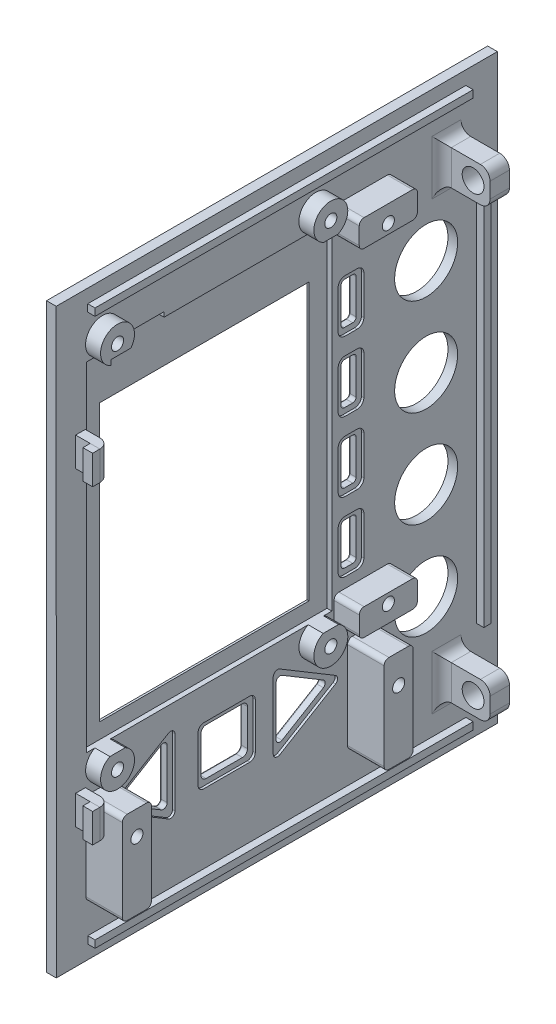
SolidWorks part; units mm, degrees
ref_plane "Front Plane" through (0, 0, 0) normal (0, 0, 1) x (1, 0, 0)
ref_plane "Top Plane" through (0, 0, 0) normal (0, 1, 0) x (1, 0, 0)
ref_plane "Right Plane" through (0, 0, 0) normal (1, 0, 0) x (0, 0, -1)
ref_plane "Plane2" through (-1175.548, -0.0877, 0) normal (-1, -0.0001, 0) x (0, 0, 1)
sketch "Sketch2" plane through (-1175.548, -0.0877, 0) normal (-1, -0.0001, 0) x (0, 0, 1)
  line L0 (-1289.195, -889.282) -> (-1289.195, -789.282) construction
  line L1 (-1204.195, -779.282) -> (-1295.195, -779.282)
  line L2 (-1204.195, -779.282) -> (-1204.195, -899.282)
  line L3 (-1204.195, -899.282) -> (-1295.195, -899.282)
  line L4 (-1295.195, -779.282) -> (-1295.195, -899.282)
  line L5 (-1289.195, -889.282) -> (-1287.685, -889.282) construction
  line L6 (-1289.195, -789.282) -> (-1287.685, -789.282) construction
  circle A0 centre (-1280.5, -869.282) radius 6.5
  circle A1 centre (-1280.5, -849.282) radius 6.5
  circle A2 centre (-1280.5, -829.282) radius 6.5
  circle A3 centre (-1280.5, -809.282) radius 6.5
  ellipse E0 centre (-1280.5, -869.282) end of major axis (-1281.15, -869.2796) minor radius 0.65 construction
  ellipse E1 centre (-1280.5, -849.282) end of major axis (-1281.15, -849.2796) minor radius 0.65 construction
  ellipse E2 centre (-1280.5, -829.282) end of major axis (-1281.15, -829.2796) minor radius 0.65 construction
  ellipse E3 centre (-1280.5, -809.282) end of major axis (-1281.15, -809.2796) minor radius 0.65 construction
  ellipse E4 centre (-1280.5, -869.282) end of major axis (-1281.15, -869.2796) minor radius 0.65
  ellipse E5 centre (-1280.5, -849.282) end of major axis (-1281.15, -849.2796) minor radius 0.65 construction
  ellipse E6 centre (-1280.5, -829.282) end of major axis (-1281.15, -829.2796) minor radius 0.65
  ellipse E7 centre (-1280.5, -809.282) end of major axis (-1281.15, -809.2796) minor radius 0.65
  dimension "D5" = 13
  dimension "D6" = 13
  dimension "D7" = 13
  dimension "D8" = 13
  dimension "D1" = 6
  dimension "D2" = 10
  dimension "D3" = 10
  dimension "D4" = 91
extrude "Boss-Extrude2" add sketch "Sketch2" along normal blind 2 contours L1 L4 L3 L2 A3 A2 A1 A0 region at (-1175.4854, -839.3697, -1248.1207)
sketch "Sketch3" plane through (-1177.548, -0.0879, 0) normal (-1, -0.0001, 0) x (0, 0, 1)
  line L12 (-1214.15, -858.982) -> (-1257.35, -858.982) construction
  line L13 (-1257.35, -858.982) -> (-1257.35, -802.002) construction
  line L14 (-1214.15, -802.002) -> (-1214.15, -858.982) construction
  line L15 (-1257.35, -802.002) -> (-1214.15, -802.002) construction
  line L16 (-1214.15, -858.982) -> (-1257.35, -858.982)
  line L17 (-1257.35, -858.982) -> (-1257.35, -802.002)
  line L18 (-1214.15, -802.002) -> (-1214.15, -858.982)
  line L19 (-1257.35, -802.002) -> (-1214.15, -802.002)
extrude "tft_cutout" cut sketch "Sketch3" against normal through all
sketch "tft_inset_cutout" plane through (-1175.548, -0.0877, 0) normal (1, 0.0001, 0) x (0, 0, -1)
  line L4 (1210.95, -792.861) -> (1210.95, -861.661) construction
  line L5 (1260.55, -792.861) -> (1210.95, -792.861) construction
  line L12 (1260.55, -861.661) -> (1260.55, -792.861) construction
  line L17 (1210.95, -861.661) -> (1260.55, -861.661) construction
  line L18 (1260.55, -861.661) -> (1260.55, -792.861) construction
  line L19 (1210.95, -861.661) -> (1260.55, -861.661) construction
  line L20 (1210.95, -792.861) -> (1210.95, -861.661) construction
  line L21 (1260.55, -792.861) -> (1210.95, -792.861) construction
  line L22 (1261.05, -792.361) -> (1210.45, -792.361)
  line L26 (1212.45, -792.861) -> (1226.45, -792.861)
  line L27 (1212.45, -792.861) -> (1212.45, -791.361)
  line L28 (1212.45, -791.361) -> (1226.45, -791.361)
  line L29 (1226.45, -792.861) -> (1226.45, -791.361)
  line L30 (1210.45, -792.361) -> (1210.45, -862.161)
  line L31 (1210.45, -862.161) -> (1261.05, -862.161)
  line L32 (1261.05, -862.161) -> (1261.05, -792.361)
  line M40 (1257.35, -858.982) -> (1214.15, -858.982)
  line M41 (1214.15, -858.982) -> (1214.15, -802.002)
  line M42 (1214.15, -802.002) -> (1257.35, -802.002)
  line M43 (1257.35, -802.002) -> (1257.35, -858.982)
  dimension "D3" = 1.5
  dimension "D4" = 0.5
  dimension "D1" = 14
  dimension "D2" = 1.5
extrude "Cut-Extrude2" cut sketch "tft_inset_cutout" against normal up to surface (1 mm away) contours L18 | L31 L32 L22 L29 L26 L27 L30 M43 M40 M41 M42 | L26 L29 L22 L27 | L22 L29 L28 L27 region at (-1175.4863, -827.3487, -1260.1879) region at (-1175.4889, -792.6987, -1219.45) region at (-1175.4889, -791.9487, -1219.45)
chamfer "Chamfer2" distance 1 angle 30 4 edges at (-1177.486, -830.5799, -1257.35) (-1177.4839, -859.0699, -1235.75) (-1177.486, -830.5799, -1214.15) (-1177.4882, -802.0899, -1235.75) first distance on face at (-1177.486, -830.5799, -1235.75)
sketch "Sketch6" plane through (-1175.548, -0.0877, 0) normal (1, 0.0001, 0) x (0, 0, -1)
  line L5 (1261.5, -864.9905) -> (1273.5, -864.9905)
  line L6 (1261.5, -864.9905) -> (1261.5, -859.4905)
  line L7 (1261.5, -859.4905) -> (1273.5, -859.4905)
  line L8 (1261.5, -864.9905) -> (1273.5, -864.9905)
  line L9 (1273.5, -864.9905) -> (1273.5, -789.9905)
  line L10 (1273.5, -789.9905) -> (1261.5, -789.9905)
  line L11 (1261.5, -789.9905) -> (1261.5, -864.9905)
  line L12 (1261.5, -864.9905) -> (1273.5, -864.9905) construction
  line L13 (1273.5, -864.9905) -> (1273.5, -789.9905) construction
  line L14 (1273.5, -789.9905) -> (1261.5, -789.9905) construction
  line L15 (1261.5, -789.9905) -> (1261.5, -864.9905) construction
  line L16 (1273.5, -864.9905) -> (1273.5, -859.4905)
  line L17 (1261.5, -789.9905) -> (1273.5, -789.9905)
  line L18 (1261.5, -789.9905) -> (1261.5, -795.4905)
  line L19 (1261.5, -795.4905) -> (1273.5, -795.4905)
  line L20 (1273.5, -789.9905) -> (1273.5, -795.4905)
  circle A0 centre (1267.5, -861.4905) radius 1.25 construction
  circle A1 centre (1267.5, -861.4905) radius 1.25 construction
  circle A2 centre (1267.5, -861.4905) radius 1.25
  circle A3 centre (1267.5, -793.4905) radius 1.25 construction
  circle A4 centre (1267.5, -793.4905) radius 1.25 construction
  circle A5 centre (1267.5, -793.4905) radius 1.25
  dimension "D2" = 2.5
  dimension "D4" = 2.5
  dimension "D3" = 2
  dimension "D5" = 2
extrude "menu_standoffs" add sketch "Sketch6" along normal up to surface (5.203 mm away)
fillet "Fillet1" radius 1 8 edges at (-1172.8871, -795.5781, -1261.5) (-1172.8871, -795.5781, -1273.5) (-1172.8875, -790.0781, -1273.5) (-1172.8875, -790.0781, -1261.5) (-1172.8824, -859.5781, -1273.5) (-1172.8824, -859.5781, -1261.5) (-1172.882, -865.0781, -1261.5) (-1172.882, -865.0781, -1273.5)
sketch "Sketch7" plane through (-1170.345, -0.0874, 0) normal (1, 0.0001, 0) x (0, 0, -1)
  circle A0 centre (1267.5, -861.4905) radius 1.25 construction
  circle A1 centre (1267.5, -793.4905) radius 1.25 construction
  circle A2 centre (1267.5, -861.4905) radius 1.25
  circle A3 centre (1267.5, -793.4905) radius 1.25
extrude "menu_standoff_holes" [suppressed] cut sketch "Sketch7" against normal blind 5 contours A2
sketch "Sketch8" plane through (-1175.548, -0.0877, 0) normal (1, 0.0001, 0) x (0, 0, -1)
  circle A0 centre (1213.75, -865.282) radius 1.55 construction
  circle A1 centre (1257.75, -865.282) radius 1.55 construction
  circle A2 centre (1257.75, -789.202) radius 1.55 construction
  circle A3 centre (1213.75, -789.2023) radius 1.55 construction
  circle A4 centre (1213.75, -865.282) radius 1.55 construction
  circle A5 centre (1257.75, -865.282) radius 1.55 construction
  circle A6 centre (1257.75, -789.202) radius 1.55 construction
  circle A7 centre (1213.75, -789.2023) radius 1.55 construction
  circle A8 centre (1213.75, -789.2023) radius 3.5
  circle A9 centre (1257.75, -789.202) radius 3.5
  circle A10 centre (1257.75, -865.282) radius 3.5
  circle A11 centre (1213.75, -865.282) radius 3.5
  circle A12 centre (1213.75, -789.2023) radius 1.25
  circle A13 centre (1213.75, -865.282) radius 1.25
  circle A14 centre (1257.75, -865.282) radius 1.25
  circle A15 centre (1257.75, -789.202) radius 1.25
  dimension "D2" = 2.5
  dimension "D1" = 7
extrude "TFT_standoffs" add sketch "Sketch8" along normal up to surface (3.09 mm away)
sketch "Sketch9" plane through (-1175.548, -0.0877, 0) normal (1, 0.0001, 0) x (0, 0, -1)
  circle A0 centre (1213.75, -789.2023) radius 1.25 construction
  circle A1 centre (1213.75, -865.282) radius 1.25 construction
  circle A2 centre (1257.75, -865.282) radius 1.25 construction
  circle A3 centre (1257.75, -789.202) radius 1.25 construction
  circle A4 centre (1213.75, -789.2023) radius 1.25
  circle A5 centre (1213.75, -865.282) radius 1.25
  circle A6 centre (1257.75, -865.282) radius 1.25
  circle A7 centre (1257.75, -789.202) radius 1.25
extrude "TFT_standoff_holes" cut sketch "Sketch9" against normal offset from surface (1 mm away) 1 up to face at (-1177.486, -830.5799, -1235.75)
extrude "Cut-Extrude5" cut sketch "Sketch5<3>" along normal through all contours L31 L32 L22 L29 L26 L27 L30 M43 M40 M41 M42 | L22 L29 L28 L27 | L26 L29 L22 L27 region at (-1175.4863, -827.3487, -1260.1879) region at (-1175.4889, -792.6987, -1219.45) region at (-1175.4889, -791.9487, -1219.45)
sketch "Sketch5<3>" plane through (-1175.548, -0.0877, 0) normal (1, 0.0001, 0) x (0, 0, -1) same geometry as "tft_inset_cutout"
sketch "Sketch10" plane through (-1175.548, -0.0877, 0) normal (1, 0.0001, 0) x (0, 0, -1)
  line L0 (1267.2535, -804.997) -> (1267.2535, -812.997) construction
  line L1 (1266.2535, -813.997) -> (1263.7535, -813.997) construction
  line L2 (1262.7535, -812.997) -> (1262.7535, -804.997) construction
  line L3 (1263.7535, -803.997) -> (1266.2535, -803.997) construction
  line L4 (1267.2535, -804.997) -> (1267.2535, -812.997) construction
  line L5 (1266.2535, -813.997) -> (1263.7535, -813.997) construction
  line L6 (1262.7535, -812.997) -> (1262.7535, -804.997) construction
  line L7 (1263.7535, -803.997) -> (1266.2535, -803.997) construction
  line L8 (1267.6535, -804.997) -> (1267.6535, -812.997)
  line L9 (1266.2535, -814.397) -> (1263.7535, -814.397)
  line L10 (1262.3535, -812.997) -> (1262.3535, -804.997)
  line L11 (1263.7535, -803.597) -> (1266.2535, -803.597)
  line L12 (1267.6535, -819.327) -> (1267.6535, -827.327)
  line L13 (1266.2535, -828.727) -> (1263.7535, -828.727)
  line L14 (1262.3535, -827.327) -> (1262.3535, -819.327)
  line L15 (1263.7535, -817.927) -> (1266.2535, -817.927)
  line L16 (1267.2535, -819.327) -> (1267.2535, -827.327) construction
  line L17 (1266.2535, -828.327) -> (1263.7535, -828.327) construction
  line L18 (1262.7535, -827.327) -> (1262.7535, -819.327) construction
  line L19 (1263.7535, -818.327) -> (1266.2535, -818.327) construction
  line L20 (1267.6535, -833.657) -> (1267.6535, -841.657)
  line L21 (1266.2535, -843.057) -> (1263.7535, -843.057)
  line L22 (1262.3535, -841.657) -> (1262.3535, -833.657)
  line L23 (1263.7535, -832.257) -> (1266.2535, -832.257)
  line L24 (1267.2535, -833.657) -> (1267.2535, -841.657) construction
  line L25 (1266.2535, -842.657) -> (1263.7535, -842.657) construction
  line L26 (1262.7535, -841.657) -> (1262.7535, -833.657) construction
  line L27 (1263.7535, -832.657) -> (1266.2535, -832.657) construction
  line L28 (1267.6535, -847.987) -> (1267.6535, -855.987)
  line L29 (1266.2535, -857.387) -> (1263.7535, -857.387)
  line L30 (1262.3535, -855.987) -> (1262.3535, -847.987)
  line L31 (1263.7535, -846.587) -> (1266.2535, -846.587)
  line L32 (1267.2535, -847.987) -> (1267.2535, -855.987) construction
  line L33 (1266.2535, -856.987) -> (1263.7535, -856.987) construction
  line L34 (1262.7535, -855.987) -> (1262.7535, -847.987) construction
  line L35 (1263.7535, -846.987) -> (1266.2535, -846.987) construction
  arc A0 (1267.2535, -804.997) -> (1266.2535, -803.997) centre (1266.2535, -804.997) ccw construction
  arc A1 (1266.2535, -813.997) -> (1267.2535, -812.997) centre (1266.2535, -812.997) ccw construction
  arc A2 (1262.7535, -812.997) -> (1263.7535, -813.997) centre (1263.7535, -812.997) ccw construction
  arc A3 (1263.7535, -803.997) -> (1262.7535, -804.997) centre (1263.7535, -804.997) ccw construction
  arc A4 (1267.2535, -804.997) -> (1266.2535, -803.997) centre (1266.2535, -804.997) ccw construction
  arc A5 (1266.2535, -813.997) -> (1267.2535, -812.997) centre (1266.2535, -812.997) ccw construction
  arc A6 (1262.7535, -812.997) -> (1263.7535, -813.997) centre (1263.7535, -812.997) ccw construction
  arc A7 (1263.7535, -803.997) -> (1262.7535, -804.997) centre (1263.7535, -804.997) ccw construction
  arc A8 (1266.2535, -814.397) -> (1267.6535, -812.997) centre (1266.2535, -812.997) ccw
  arc A9 (1262.3535, -812.997) -> (1263.7535, -814.397) centre (1263.7535, -812.997) ccw
  arc A10 (1263.7535, -803.597) -> (1262.3535, -804.997) centre (1263.7535, -804.997) ccw
  arc A11 (1267.6535, -804.997) -> (1266.2535, -803.597) centre (1266.2535, -804.997) ccw
  arc A12 (1266.2535, -828.727) -> (1267.6535, -827.327) centre (1266.2535, -827.327) ccw
  arc A13 (1262.3535, -827.327) -> (1263.7535, -828.727) centre (1263.7535, -827.327) ccw
  arc A14 (1263.7535, -817.927) -> (1262.3535, -819.327) centre (1263.7535, -819.327) ccw
  arc A15 (1267.6535, -819.327) -> (1266.2535, -817.927) centre (1266.2535, -819.327) ccw
  arc A16 (1267.2535, -819.327) -> (1266.2535, -818.327) centre (1266.2535, -819.327) ccw construction
  arc A17 (1266.2535, -828.327) -> (1267.2535, -827.327) centre (1266.2535, -827.327) ccw construction
  arc A18 (1262.7535, -827.327) -> (1263.7535, -828.327) centre (1263.7535, -827.327) ccw construction
  arc A19 (1263.7535, -818.327) -> (1262.7535, -819.327) centre (1263.7535, -819.327) ccw construction
  arc A20 (1266.2535, -843.057) -> (1267.6535, -841.657) centre (1266.2535, -841.657) ccw
  arc A21 (1262.3535, -841.657) -> (1263.7535, -843.057) centre (1263.7535, -841.657) ccw
  arc A22 (1263.7535, -832.257) -> (1262.3535, -833.657) centre (1263.7535, -833.657) ccw
  arc A23 (1267.6535, -833.657) -> (1266.2535, -832.257) centre (1266.2535, -833.657) ccw
  arc A24 (1267.2535, -833.657) -> (1266.2535, -832.657) centre (1266.2535, -833.657) ccw construction
  arc A25 (1266.2535, -842.657) -> (1267.2535, -841.657) centre (1266.2535, -841.657) ccw construction
  arc A26 (1262.7535, -841.657) -> (1263.7535, -842.657) centre (1263.7535, -841.657) ccw construction
  arc A27 (1263.7535, -832.657) -> (1262.7535, -833.657) centre (1263.7535, -833.657) ccw construction
  arc A28 (1266.2535, -857.387) -> (1267.6535, -855.987) centre (1266.2535, -855.987) ccw
  arc A29 (1262.3535, -855.987) -> (1263.7535, -857.387) centre (1263.7535, -855.987) ccw
  arc A30 (1263.7535, -846.587) -> (1262.3535, -847.987) centre (1263.7535, -847.987) ccw
  arc A31 (1267.6535, -847.987) -> (1266.2535, -846.587) centre (1266.2535, -847.987) ccw
  arc A32 (1267.2535, -847.987) -> (1266.2535, -846.987) centre (1266.2535, -847.987) ccw construction
  arc A33 (1266.2535, -856.987) -> (1267.2535, -855.987) centre (1266.2535, -855.987) ccw construction
  arc A34 (1262.7535, -855.987) -> (1263.7535, -856.987) centre (1263.7535, -855.987) ccw construction
  arc A35 (1263.7535, -846.987) -> (1262.7535, -847.987) centre (1263.7535, -847.987) ccw construction
  dimension "D1" = 0.4
  dimension "D2" = 4
extrude "menu_panel_inset" cut sketch "Sketch10" against normal offset from surface 1.5 and the other way through all up to face at (-1177.486, -830.5799, -1235.75)
sketch "Sketch11" plane through (-1177.548, -0.0879, 0) normal (-1, -0.0001, 0) x (0, 0, 1)
  line L0 (-1265.8535, -812.997) -> (-1264.1535, -812.997) construction
  line L1 (-1266.2535, -805.397) -> (-1266.2535, -812.597) construction
  line L2 (-1265.8535, -804.997) -> (-1264.1535, -804.997) construction
  line L3 (-1263.7535, -805.397) -> (-1263.7535, -812.597) construction
  line L4 (-1265.8535, -812.997) -> (-1264.1535, -812.997) construction
  line L5 (-1266.2535, -805.397) -> (-1266.2535, -812.597) construction
  line L6 (-1265.8535, -804.997) -> (-1264.1535, -804.997) construction
  line L7 (-1263.7535, -805.397) -> (-1263.7535, -812.597) construction
  line L8 (-1263.4535, -805.397) -> (-1263.4535, -812.597)
  line L9 (-1265.8535, -813.297) -> (-1264.1535, -813.297)
  line L10 (-1266.5535, -805.397) -> (-1266.5535, -812.597)
  line L11 (-1265.8535, -804.697) -> (-1264.1535, -804.697)
  line L12 (-1263.4535, -819.727) -> (-1263.4535, -826.927)
  line L13 (-1265.8535, -827.627) -> (-1264.1535, -827.627)
  line L14 (-1266.5535, -819.727) -> (-1266.5535, -826.927)
  line L15 (-1265.8535, -819.027) -> (-1264.1535, -819.027)
  line L16 (-1265.8535, -827.327) -> (-1264.1535, -827.327) construction
  line L17 (-1266.2535, -819.727) -> (-1266.2535, -826.927) construction
  line L18 (-1265.8535, -819.327) -> (-1264.1535, -819.327) construction
  line L19 (-1263.7535, -819.727) -> (-1263.7535, -826.927) construction
  line L20 (-1263.4535, -834.057) -> (-1263.4535, -841.257)
  line L21 (-1265.8535, -841.957) -> (-1264.1535, -841.957)
  line L22 (-1266.5535, -834.057) -> (-1266.5535, -841.257)
  line L23 (-1265.8535, -833.357) -> (-1264.1535, -833.357)
  line L24 (-1265.8535, -841.657) -> (-1264.1535, -841.657) construction
  line L25 (-1266.2535, -834.057) -> (-1266.2535, -841.257) construction
  line L26 (-1265.8535, -833.657) -> (-1264.1535, -833.657) construction
  line L27 (-1263.7535, -834.057) -> (-1263.7535, -841.257) construction
  line L28 (-1263.4535, -848.387) -> (-1263.4535, -855.587)
  line L29 (-1265.8535, -856.287) -> (-1264.1535, -856.287)
  line L30 (-1266.5535, -848.387) -> (-1266.5535, -855.587)
  line L31 (-1265.8535, -847.687) -> (-1264.1535, -847.687)
  line L32 (-1265.8535, -855.987) -> (-1264.1535, -855.987) construction
  line L33 (-1266.2535, -848.387) -> (-1266.2535, -855.587) construction
  line L34 (-1265.8535, -847.987) -> (-1264.1535, -847.987) construction
  line L35 (-1263.7535, -848.387) -> (-1263.7535, -855.587) construction
  arc A0 (-1264.1535, -812.997) -> (-1263.7535, -812.597) centre (-1264.1535, -812.597) ccw construction
  arc A1 (-1266.2535, -812.597) -> (-1265.8535, -812.997) centre (-1265.8535, -812.597) ccw construction
  arc A2 (-1265.8535, -804.997) -> (-1266.2535, -805.397) centre (-1265.8535, -805.397) ccw construction
  arc A3 (-1263.7535, -805.397) -> (-1264.1535, -804.997) centre (-1264.1535, -805.397) ccw construction
  arc A4 (-1264.1535, -812.997) -> (-1263.7535, -812.597) centre (-1264.1535, -812.597) ccw construction
  arc A5 (-1266.2535, -812.597) -> (-1265.8535, -812.997) centre (-1265.8535, -812.597) ccw construction
  arc A6 (-1265.8535, -804.997) -> (-1266.2535, -805.397) centre (-1265.8535, -805.397) ccw construction
  arc A7 (-1263.7535, -805.397) -> (-1264.1535, -804.997) centre (-1264.1535, -805.397) ccw construction
  arc A8 (-1264.1535, -813.297) -> (-1263.4535, -812.597) centre (-1264.1535, -812.597) ccw
  arc A9 (-1266.5535, -812.597) -> (-1265.8535, -813.297) centre (-1265.8535, -812.597) ccw
  arc A10 (-1265.8535, -804.697) -> (-1266.5535, -805.397) centre (-1265.8535, -805.397) ccw
  arc A11 (-1263.4535, -805.397) -> (-1264.1535, -804.697) centre (-1264.1535, -805.397) ccw
  arc A12 (-1264.1535, -827.627) -> (-1263.4535, -826.927) centre (-1264.1535, -826.927) ccw
  arc A13 (-1266.5535, -826.927) -> (-1265.8535, -827.627) centre (-1265.8535, -826.927) ccw
  arc A14 (-1265.8535, -819.027) -> (-1266.5535, -819.727) centre (-1265.8535, -819.727) ccw
  arc A15 (-1263.4535, -819.727) -> (-1264.1535, -819.027) centre (-1264.1535, -819.727) ccw
  arc A16 (-1264.1535, -827.327) -> (-1263.7535, -826.927) centre (-1264.1535, -826.927) ccw construction
  arc A17 (-1266.2535, -826.927) -> (-1265.8535, -827.327) centre (-1265.8535, -826.927) ccw construction
  arc A18 (-1265.8535, -819.327) -> (-1266.2535, -819.727) centre (-1265.8535, -819.727) ccw construction
  arc A19 (-1263.7535, -819.727) -> (-1264.1535, -819.327) centre (-1264.1535, -819.727) ccw construction
  arc A20 (-1264.1535, -841.957) -> (-1263.4535, -841.257) centre (-1264.1535, -841.257) ccw
  arc A21 (-1266.5535, -841.257) -> (-1265.8535, -841.957) centre (-1265.8535, -841.257) ccw
  arc A22 (-1265.8535, -833.357) -> (-1266.5535, -834.057) centre (-1265.8535, -834.057) ccw
  arc A23 (-1263.4535, -834.057) -> (-1264.1535, -833.357) centre (-1264.1535, -834.057) ccw
  arc A24 (-1264.1535, -841.657) -> (-1263.7535, -841.257) centre (-1264.1535, -841.257) ccw construction
  arc A25 (-1266.2535, -841.257) -> (-1265.8535, -841.657) centre (-1265.8535, -841.257) ccw construction
  arc A26 (-1265.8535, -833.657) -> (-1266.2535, -834.057) centre (-1265.8535, -834.057) ccw construction
  arc A27 (-1263.7535, -834.057) -> (-1264.1535, -833.657) centre (-1264.1535, -834.057) ccw construction
  arc A28 (-1264.1535, -856.287) -> (-1263.4535, -855.587) centre (-1264.1535, -855.587) ccw
  arc A29 (-1266.5535, -855.587) -> (-1265.8535, -856.287) centre (-1265.8535, -855.587) ccw
  arc A30 (-1265.8535, -847.687) -> (-1266.5535, -848.387) centre (-1265.8535, -848.387) ccw
  arc A31 (-1263.4535, -848.387) -> (-1264.1535, -847.687) centre (-1264.1535, -848.387) ccw
  arc A32 (-1264.1535, -855.987) -> (-1263.7535, -855.587) centre (-1264.1535, -855.587) ccw construction
  arc A33 (-1266.2535, -855.587) -> (-1265.8535, -855.987) centre (-1265.8535, -855.587) ccw construction
  arc A34 (-1265.8535, -847.987) -> (-1266.2535, -848.387) centre (-1265.8535, -848.387) ccw construction
  arc A35 (-1263.7535, -848.387) -> (-1264.1535, -847.987) centre (-1264.1535, -848.387) ccw construction
  dimension "D1" = 0.3
  dimension "D2" = 4
extrude "menu_panel_cutout" cut sketch "Sketch11" against normal through all
fillet "Fillet2" radius 0.25 32 edges at (-1177.4876, -809.0849, -1263.4535) (-1177.4873, -813.1798, -1263.6586) (-1177.4873, -813.3849, -1265.0035) (-1177.4873, -813.1798, -1266.3485) (-1177.4876, -809.0849, -1266.5535) (-1177.4879, -804.9899, -1266.3485) (-1177.488, -804.7849, -1265.0035) (-1177.4862, -827.7149, -1265.0035) (-1177.4863, -827.5098, -1266.3485) (-1177.4866, -823.4149, -1266.5535) (-1177.4869, -819.3199, -1266.3485) (-1177.4869, -819.1149, -1265.0035) (-1177.4869, -819.3199, -1263.6586) (-1177.4866, -823.4149, -1263.4535) (-1177.4852, -842.0449, -1265.0035) (-1177.4852, -841.8398, -1266.3485) (-1177.4855, -837.7449, -1266.5535) (-1177.4858, -833.6499, -1266.3485) (-1177.4858, -833.4449, -1265.0035) (-1177.4858, -833.6499, -1263.6586) (-1177.4855, -837.7449, -1263.4535) (-1177.4844, -852.0749, -1263.4535) (-1177.4841, -856.1698, -1263.6586) (-1177.4841, -856.3749, -1265.0035) (-1177.4841, -856.1698, -1266.3485) (-1177.4844, -852.0749, -1266.5535) (-1177.4847, -847.9799, -1266.3485) (-1177.4847, -847.7749, -1265.0035) (-1177.4879, -804.9899, -1263.6586) (-1177.4863, -827.5098, -1263.6586) (-1177.4852, -841.8398, -1263.6586) (-1177.4847, -847.9799, -1263.6586)
sketch "Sketch12" plane through (-1175.548, -0.0877, 0) normal (1, 0.0001, 0) x (0, 0, -1)
  line L0 (1270.2797, -888.782) -> (1210.2797, -888.782) construction
  line L1 (1270.2797, -868.782) -> (1264.2797, -868.782)
  line L2 (1270.2797, -868.782) -> (1270.2797, -888.782)
  line L3 (1270.2797, -888.782) -> (1264.2797, -888.782)
  line L4 (1264.2797, -868.782) -> (1264.2797, -888.782)
  line L6 (1210.2797, -888.782) -> (1216.2797, -888.782)
  line L7 (1210.2797, -888.782) -> (1210.2797, -869.782)
  line L8 (1210.2797, -869.782) -> (1216.2797, -869.782)
  line L9 (1216.2797, -888.782) -> (1216.2797, -869.782)
  line L10 (1210.2797, -868.782) -> (1270.2797, -868.782) construction
  circle A0 centre (1267.2797, -874.782) radius 1.25
  circle A1 centre (1213.2797, -874.782) radius 1.25
  dimension "D1" = 6
  dimension "D2" = 2.5
  dimension "D4" = 2.5
  dimension "D3" = 6
  dimension "D5" = 1
extrude "selector_standoffs" add sketch "Sketch12" along normal up to surface (7.55 mm away) contours L6 L9 L8 L7 A1 | L1 L4 L3 L2 A0 region at (-1175.4824, -879.0403, -1267.2797) region at (-1175.4824, -879.5722, -1213.2797)
fillet "Fillet3" radius 1 8 edges at (-1171.7067, -888.8694, -1270.2797) (-1171.7082, -868.8694, -1270.2797) (-1171.7082, -868.8694, -1264.2797) (-1171.7067, -888.8694, -1264.2797) (-1171.7067, -888.8694, -1216.2797) (-1171.7067, -888.8694, -1210.2797) (-1171.7081, -869.8694, -1210.2797) (-1171.7081, -869.8694, -1216.2797)
sketch "Sketch13" plane through (-1175.548, -0.0877, 0) normal (1, 0.0001, 0) x (0, 0, -1)
  line L0 (1218.0014, -875.2178) -> (1226.5296, -880.3347) construction
  line L1 (1227.2868, -879.906) -> (1227.2868, -869.6722) construction
  line L2 (1226.5296, -869.2434) -> (1218.0014, -874.3603) construction
  line L3 (1234.85, -871.0391) -> (1234.85, -878.5391) construction
  line L4 (1235.6, -879.2891) -> (1243.1, -879.2891) construction
  line L5 (1243.1, -870.2891) -> (1235.6, -870.2891) construction
  line L6 (1243.85, -878.5391) -> (1243.85, -871.0391) construction
  line L7 (1259.6354, -874.3603) -> (1251.1072, -869.2434) construction
  line L8 (1250.35, -869.6722) -> (1250.35, -879.906) construction
  line L9 (1251.1072, -880.3347) -> (1259.6354, -875.2178) construction
  line L10 (1218.0014, -875.2178) -> (1226.5296, -880.3347) construction
  line L11 (1227.2868, -879.906) -> (1227.2868, -869.6722) construction
  line L12 (1226.5296, -869.2434) -> (1218.0014, -874.3603) construction
  line L13 (1234.85, -871.0391) -> (1234.85, -878.5391) construction
  line L14 (1235.6, -879.2891) -> (1243.1, -879.2891) construction
  line L15 (1243.1, -870.2891) -> (1235.6, -870.2891) construction
  line L16 (1243.85, -878.5391) -> (1243.85, -871.0391) construction
  line L17 (1259.6354, -874.3603) -> (1251.1072, -869.2434) construction
  line L18 (1250.35, -869.6722) -> (1250.35, -879.906) construction
  line L19 (1251.1072, -880.3347) -> (1259.6354, -875.2178) construction
  line L20 (1217.847, -875.4751) -> (1226.3752, -880.592)
  line L21 (1227.5868, -879.906) -> (1227.5868, -869.6722)
  line L22 (1226.3752, -868.9862) -> (1217.847, -874.1031)
  line L23 (1234.55, -871.0391) -> (1234.55, -878.5391)
  line L24 (1235.6, -879.5891) -> (1243.1, -879.5891)
  line L25 (1244.15, -878.5391) -> (1244.15, -871.0391)
  line L26 (1243.1, -869.9891) -> (1235.6, -869.9891)
  line L27 (1259.7898, -874.1031) -> (1251.2616, -868.9862)
  line L28 (1250.05, -869.6722) -> (1250.05, -879.906)
  line L29 (1251.2616, -880.592) -> (1259.7898, -875.4751)
  arc A0 (1218.0014, -874.3603) -> (1218.0014, -875.2178) centre (1218.2586, -874.7891) ccw construction
  arc A1 (1226.5296, -880.3347) -> (1227.2868, -879.906) centre (1226.7868, -879.906) ccw construction
  arc A2 (1227.2868, -869.6722) -> (1226.5296, -869.2434) centre (1226.7868, -869.6722) ccw construction
  arc A3 (1235.6, -870.2891) -> (1234.85, -871.0391) centre (1235.6, -871.0391) ccw construction
  arc A4 (1234.85, -878.5391) -> (1235.6, -879.2891) centre (1235.6, -878.5391) ccw construction
  arc A5 (1243.1, -879.2891) -> (1243.85, -878.5391) centre (1243.1, -878.5391) ccw construction
  arc A6 (1243.85, -871.0391) -> (1243.1, -870.2891) centre (1243.1, -871.0391) ccw construction
  arc A7 (1259.6354, -875.2178) -> (1259.6354, -874.3603) centre (1259.3782, -874.7891) ccw construction
  arc A8 (1251.1072, -869.2434) -> (1250.35, -869.6722) centre (1250.85, -869.6722) ccw construction
  arc A9 (1250.35, -879.906) -> (1251.1072, -880.3347) centre (1250.85, -879.906) ccw construction
  arc A10 (1218.0014, -874.3603) -> (1218.0014, -875.2178) centre (1218.2586, -874.7891) ccw construction
  arc A11 (1226.5296, -880.3347) -> (1227.2868, -879.906) centre (1226.7868, -879.906) ccw construction
  arc A12 (1227.2868, -869.6722) -> (1226.5296, -869.2434) centre (1226.7868, -869.6722) ccw construction
  arc A13 (1235.6, -870.2891) -> (1234.85, -871.0391) centre (1235.6, -871.0391) ccw construction
  arc A14 (1234.85, -878.5391) -> (1235.6, -879.2891) centre (1235.6, -878.5391) ccw construction
  arc A15 (1243.1, -879.2891) -> (1243.85, -878.5391) centre (1243.1, -878.5391) ccw construction
  arc A16 (1243.85, -871.0391) -> (1243.1, -870.2891) centre (1243.1, -871.0391) ccw construction
  arc A17 (1259.6354, -875.2178) -> (1259.6354, -874.3603) centre (1259.3782, -874.7891) ccw construction
  arc A18 (1251.1072, -869.2434) -> (1250.35, -869.6722) centre (1250.85, -869.6722) ccw construction
  arc A19 (1250.35, -879.906) -> (1251.1072, -880.3347) centre (1250.85, -879.906) ccw construction
  arc A20 (1226.3752, -880.592) -> (1227.5868, -879.906) centre (1226.7868, -879.906) ccw
  arc A21 (1227.5868, -869.6722) -> (1226.3752, -868.9862) centre (1226.7868, -869.6722) ccw
  arc A22 (1217.847, -874.1031) -> (1217.847, -875.4751) centre (1218.2586, -874.7891) ccw
  arc A23 (1234.55, -878.5391) -> (1235.6, -879.5891) centre (1235.6, -878.5391) ccw
  arc A24 (1243.1, -879.5891) -> (1244.15, -878.5391) centre (1243.1, -878.5391) ccw
  arc A25 (1244.15, -871.0391) -> (1243.1, -869.9891) centre (1243.1, -871.0391) ccw
  arc A26 (1235.6, -869.9891) -> (1234.55, -871.0391) centre (1235.6, -871.0391) ccw
  arc A27 (1251.2616, -868.9862) -> (1250.05, -869.6722) centre (1250.85, -869.6722) ccw
  arc A28 (1250.05, -879.906) -> (1251.2616, -880.592) centre (1250.85, -879.906) ccw
  arc A29 (1259.7898, -875.4751) -> (1259.7898, -874.1031) centre (1259.3782, -874.7891) ccw
  dimension "D1" = 0.3
  dimension "D2" = 0.3
  dimension "D3" = 0.3
extrude "selector_cutout" cut sketch "Sketch13" against normal through all
fillet "Fillet4" radius 0.25 20 edges at (-1177.4824, -879.677, -1239.35) (-1177.4824, -879.3694, -1234.8575) (-1177.4827, -874.877, -1234.55) (-1177.4831, -870.3845, -1234.8575) (-1177.4831, -870.077, -1239.35) (-1177.4831, -870.3845, -1243.8424) (-1177.4827, -874.877, -1244.15) (-1177.4832, -869.0639, -1250.4558) (-1177.483, -871.6325, -1255.5257) (-1177.4827, -874.877, -1260.1782) (-1177.4825, -878.1214, -1255.5257) (-1177.4823, -880.69, -1250.4558) (-1177.4824, -879.3694, -1243.8424) (-1177.4827, -874.877, -1250.05) (-1177.4825, -878.1214, -1222.1111) (-1177.4827, -874.877, -1217.4586) (-1177.483, -871.6325, -1222.1111) (-1177.4832, -869.0639, -1227.181) (-1177.4827, -874.877, -1227.5868) (-1177.4823, -880.69, -1227.181)
sketch "Sketch17" plane through (-1175.548, -0.0877, 0) normal (1, 0.0001, 0) x (0, 0, -1)
  line L18 (1220.3082, -871.8101) -> (1216.0577, -874.3603) construction
  line L19 (1216.0577, -875.2178) -> (1220.3082, -877.7681) construction
  line L20 (1220.1868, -877.5537) -> (1220.1868, -872.0244) construction
  line L21 (1228.2868, -881.6722) -> (1228.2868, -867.906) construction
  line L22 (1227.5296, -867.4772) -> (1220.4505, -871.7247) construction
  line L23 (1220.5791, -871.6891) -> (1226.1368, -871.6891) construction
  line L24 (1226.3868, -871.9391) -> (1226.3868, -877.6391) construction
  line L25 (1226.1368, -877.8891) -> (1220.5791, -877.8891) construction
  line L26 (1220.4505, -877.8535) -> (1227.5296, -882.1009) construction
  line L27 (1220.3082, -871.8101) -> (1216.0577, -874.3603) construction
  line L28 (1216.0577, -875.2178) -> (1220.3082, -877.7681) construction
  line L29 (1220.1868, -877.5537) -> (1220.1868, -872.0244) construction
  line L30 (1228.2868, -881.6722) -> (1228.2868, -867.906) construction
  line L31 (1257.3286, -877.7681) -> (1261.5791, -875.2178) construction
  line L32 (1261.5791, -874.3603) -> (1257.3286, -871.8101) construction
  line L33 (1257.45, -872.0244) -> (1257.45, -877.5537) construction
  line L34 (1249.35, -867.906) -> (1249.35, -881.6722) construction
  line L35 (1250.1072, -882.1009) -> (1257.1863, -877.8535) construction
  line L36 (1257.0577, -877.8891) -> (1251.5, -877.8891) construction
  line L37 (1251.25, -877.6391) -> (1251.25, -871.9391) construction
  line L38 (1251.5, -871.6891) -> (1257.0577, -871.6891) construction
  line L39 (1257.1863, -871.7247) -> (1250.1072, -867.4772) construction
  line L40 (1233.85, -870.0391) -> (1233.85, -879.5391) construction
  line L41 (1234.6, -880.2891) -> (1244.1, -880.2891) construction
  line L42 (1244.85, -879.5391) -> (1244.85, -870.0391) construction
  line L43 (1244.1, -869.2891) -> (1234.6, -869.2891) construction
  line L44 (1257.3286, -877.7681) -> (1261.5791, -875.2178) construction
  line L45 (1261.5791, -874.3603) -> (1257.3286, -871.8101) construction
  line L46 (1257.45, -872.0244) -> (1257.45, -877.5537) construction
  line L47 (1249.35, -867.906) -> (1249.35, -881.6722) construction
  line L48 (1250.1072, -882.1009) -> (1257.1863, -877.8535) construction
  line L49 (1257.0577, -877.8891) -> (1251.5, -877.8891) construction
  line L50 (1251.25, -877.6391) -> (1251.25, -871.9391) construction
  line L51 (1251.5, -871.6891) -> (1257.0577, -871.6891) construction
  line L52 (1257.1863, -871.7247) -> (1250.1072, -867.4772) construction
  line L53 (1233.85, -870.0391) -> (1233.85, -879.5391) construction
  line L54 (1234.6, -880.2891) -> (1244.1, -880.2891) construction
  line L55 (1244.85, -879.5391) -> (1244.85, -870.0391) construction
  line L56 (1244.1, -869.2891) -> (1234.6, -869.2891) construction
  line L57 (1257.1863, -877.8535) -> (1257.3286, -877.7681)
  line L58 (1257.3286, -871.8101) -> (1257.1863, -871.7247)
  line L59 (1227.5296, -867.4772) -> (1220.4505, -871.7247) construction
  line L60 (1220.5791, -871.6891) -> (1226.1368, -871.6891) construction
  line L61 (1226.3868, -871.9391) -> (1226.3868, -877.6391) construction
  line L62 (1226.1368, -877.8891) -> (1220.5791, -877.8891) construction
  line L63 (1220.4505, -877.8535) -> (1227.5296, -882.1009) construction
  line L64 (1220.3082, -871.8101) -> (1220.4505, -871.7247)
  line L65 (1220.4505, -877.8535) -> (1220.3082, -877.7681)
  line L66 (1257.3921, -878.1965) -> (1257.5344, -878.1111)
  line L67 (1257.5344, -871.4671) -> (1257.3921, -871.3817)
  line L68 (1220.514, -872.1531) -> (1220.6563, -872.0677)
  line L69 (1220.6563, -877.5105) -> (1220.514, -877.4251)
  line L70 (1220.1024, -871.4671) -> (1215.8519, -874.0173)
  line L71 (1215.8519, -875.5608) -> (1220.1024, -878.1111)
  line L72 (1220.5868, -877.4811) -> (1220.5868, -872.0971)
  line L73 (1220.2447, -878.1965) -> (1227.3238, -882.4439)
  line L74 (1228.6868, -881.6722) -> (1228.6868, -867.906)
  line L75 (1227.3238, -867.1342) -> (1220.2447, -871.3817)
  line L76 (1257.5344, -878.1111) -> (1261.7849, -875.5608)
  line L77 (1261.7849, -874.0173) -> (1257.5344, -871.4671)
  line L78 (1257.05, -872.0971) -> (1257.05, -877.4811)
  line L79 (1257.3921, -871.3817) -> (1250.313, -867.1342)
  line L80 (1248.95, -867.906) -> (1248.95, -881.6722)
  line L81 (1250.313, -882.4439) -> (1257.3921, -878.1965)
  line L82 (1257.0213, -877.4891) -> (1251.65, -877.4891)
  line L83 (1251.65, -877.4891) -> (1251.65, -872.0891)
  line L84 (1251.65, -872.0891) -> (1257.0213, -872.0891)
  line L85 (1233.45, -870.0391) -> (1233.45, -879.5391)
  line L86 (1234.6, -880.6891) -> (1244.1, -880.6891)
  line L87 (1245.25, -879.5391) -> (1245.25, -870.0391)
  line L88 (1244.1, -868.8891) -> (1234.6, -868.8891)
  line L89 (1220.6155, -872.0891) -> (1225.9868, -872.0891)
  line L90 (1225.9868, -872.0891) -> (1225.9868, -877.4891)
  line L91 (1225.9868, -877.4891) -> (1220.6155, -877.4891)
  line L92 (1220.1024, -878.1111) -> (1220.2447, -878.1965)
  line L93 (1220.2447, -871.3817) -> (1220.1024, -871.4671)
  arc A18 (1216.0577, -874.3603) -> (1216.0577, -875.2178) centre (1216.315, -874.7891) ccw construction
  arc A19 (1220.1868, -877.5537) -> (1220.3082, -877.7681) centre (1220.4368, -877.5537) ccw construction
  arc A20 (1220.3082, -871.8101) -> (1220.1868, -872.0244) centre (1220.4368, -872.0244) ccw construction
  arc A21 (1228.2868, -867.906) -> (1227.5296, -867.4772) centre (1227.7868, -867.906) ccw construction
  arc A22 (1220.5791, -871.6891) -> (1220.4505, -871.7247) centre (1220.5791, -871.9391) ccw construction
  arc A23 (1226.3868, -871.9391) -> (1226.1368, -871.6891) centre (1226.1368, -871.9391) ccw construction
  arc A24 (1226.1368, -877.8891) -> (1226.3868, -877.6391) centre (1226.1368, -877.6391) ccw construction
  arc A25 (1220.4505, -877.8535) -> (1220.5791, -877.8891) centre (1220.5791, -877.6391) ccw construction
  arc A26 (1227.5296, -882.1009) -> (1228.2868, -881.6722) centre (1227.7868, -881.6722) ccw construction
  arc A27 (1261.5791, -875.2178) -> (1261.5791, -874.3603) centre (1261.3218, -874.7891) ccw construction
  arc A28 (1257.45, -872.0244) -> (1257.3286, -871.8101) centre (1257.2, -872.0244) ccw construction
  arc A29 (1257.3286, -877.7681) -> (1257.45, -877.5537) centre (1257.2, -877.5537) ccw construction
  arc A30 (1249.35, -881.6722) -> (1250.1072, -882.1009) centre (1249.85, -881.6722) ccw construction
  arc A31 (1257.0577, -877.8891) -> (1257.1863, -877.8535) centre (1257.0577, -877.6391) ccw construction
  arc A32 (1251.25, -877.6391) -> (1251.5, -877.8891) centre (1251.5, -877.6391) ccw construction
  arc A33 (1251.5, -871.6891) -> (1251.25, -871.9391) centre (1251.5, -871.9391) ccw construction
  arc A34 (1257.1863, -871.7247) -> (1257.0577, -871.6891) centre (1257.0577, -871.9391) ccw construction
  arc A35 (1250.1072, -867.4772) -> (1249.35, -867.906) centre (1249.85, -867.906) ccw construction
  arc A36 (1233.85, -879.5391) -> (1234.6, -880.2891) centre (1234.6, -879.5391) ccw construction
  arc A37 (1244.1, -880.2891) -> (1244.85, -879.5391) centre (1244.1, -879.5391) ccw construction
  arc A38 (1244.85, -870.0391) -> (1244.1, -869.2891) centre (1244.1, -870.0391) ccw construction
  arc A39 (1234.6, -869.2891) -> (1233.85, -870.0391) centre (1234.6, -870.0391) ccw construction
  arc A40 (1261.5791, -875.2178) -> (1261.5791, -874.3603) centre (1261.3218, -874.7891) ccw construction
  arc A41 (1257.45, -872.0244) -> (1257.3286, -871.8101) centre (1257.2, -872.0244) ccw construction
  arc A42 (1257.3286, -877.7681) -> (1257.45, -877.5537) centre (1257.2, -877.5537) ccw construction
  arc A43 (1249.35, -881.6722) -> (1250.1072, -882.1009) centre (1249.85, -881.6722) ccw construction
  arc A44 (1257.0577, -877.8891) -> (1257.1863, -877.8535) centre (1257.0577, -877.6391) ccw construction
  arc A45 (1251.25, -877.6391) -> (1251.5, -877.8891) centre (1251.5, -877.6391) ccw construction
  arc A46 (1251.5, -871.6891) -> (1251.25, -871.9391) centre (1251.5, -871.9391) ccw construction
  arc A47 (1257.1863, -871.7247) -> (1257.0577, -871.6891) centre (1257.0577, -871.9391) ccw construction
  arc A48 (1250.1072, -867.4772) -> (1249.35, -867.906) centre (1249.85, -867.906) ccw construction
  arc A49 (1233.85, -879.5391) -> (1234.6, -880.2891) centre (1234.6, -879.5391) ccw construction
  arc A50 (1244.1, -880.2891) -> (1244.85, -879.5391) centre (1244.1, -879.5391) ccw construction
  arc A51 (1244.85, -870.0391) -> (1244.1, -869.2891) centre (1244.1, -870.0391) ccw construction
  arc A52 (1234.6, -869.2891) -> (1233.85, -870.0391) centre (1234.6, -870.0391) ccw construction
  arc A53 (1216.0577, -874.3603) -> (1216.0577, -875.2178) centre (1216.315, -874.7891) ccw construction
  arc A54 (1220.1868, -877.5537) -> (1220.3082, -877.7681) centre (1220.4368, -877.5537) ccw construction
  arc A55 (1220.3082, -871.8101) -> (1220.1868, -872.0244) centre (1220.4368, -872.0244) ccw construction
  arc A56 (1228.2868, -867.906) -> (1227.5296, -867.4772) centre (1227.7868, -867.906) ccw construction
  arc A57 (1220.5791, -871.6891) -> (1220.4505, -871.7247) centre (1220.5791, -871.9391) ccw construction
  arc A58 (1226.3868, -871.9391) -> (1226.1368, -871.6891) centre (1226.1368, -871.9391) ccw construction
  arc A59 (1226.1368, -877.8891) -> (1226.3868, -877.6391) centre (1226.1368, -877.6391) ccw construction
  arc A60 (1220.4505, -877.8535) -> (1220.5791, -877.8891) centre (1220.5791, -877.6391) ccw construction
  arc A61 (1227.5296, -882.1009) -> (1228.2868, -881.6722) centre (1227.7868, -881.6722) ccw construction
  arc A62 (1215.8519, -874.0173) -> (1215.8519, -875.5608) centre (1216.315, -874.7891) ccw
  arc A63 (1220.5868, -877.4811) -> (1220.5868, -877.4811) centre (1220.5868, -877.4811) cw
  arc A64 (1220.5868, -872.0971) -> (1220.5868, -872.0971) centre (1220.5868, -872.0971) cw
  arc A65 (1227.3238, -882.4439) -> (1228.6868, -881.6722) centre (1227.7868, -881.6722) ccw
  arc A66 (1228.6868, -867.906) -> (1227.3238, -867.1342) centre (1227.7868, -867.906) ccw
  arc A67 (1261.7849, -875.5608) -> (1261.7849, -874.0173) centre (1261.3218, -874.7891) ccw
  arc A68 (1257.05, -872.0971) -> (1257.05, -872.0971) centre (1257.05, -872.0971) cw
  arc A69 (1257.05, -877.4811) -> (1257.05, -877.4811) centre (1257.05, -877.4811) cw
  arc A70 (1250.313, -867.1342) -> (1248.95, -867.906) centre (1249.85, -867.906) ccw
  arc A71 (1248.95, -881.6722) -> (1250.313, -882.4439) centre (1249.85, -881.6722) ccw
  arc A72 (1257.0213, -877.4891) -> (1257.0213, -877.4891) centre (1257.0213, -877.4891) cw
  arc A73 (1251.65, -877.4891) -> (1251.65, -877.4891) centre (1251.65, -877.4891) ccw
  arc A74 (1251.65, -872.0891) -> (1251.65, -872.0891) centre (1251.65, -872.0891) ccw
  arc A75 (1257.0213, -872.0891) -> (1257.0213, -872.0891) centre (1257.0213, -872.0891) cw
  arc A76 (1233.45, -879.5391) -> (1234.6, -880.6891) centre (1234.6, -879.5391) ccw
  arc A77 (1244.1, -880.6891) -> (1245.25, -879.5391) centre (1244.1, -879.5391) ccw
  arc A78 (1245.25, -870.0391) -> (1244.1, -868.8891) centre (1244.1, -870.0391) ccw
  arc A79 (1234.6, -868.8891) -> (1233.45, -870.0391) centre (1234.6, -870.0391) ccw
  arc A80 (1220.6155, -872.0891) -> (1220.6155, -872.0891) centre (1220.6155, -872.0891) cw
  arc A81 (1225.9868, -872.0891) -> (1225.9868, -872.0891) centre (1225.9868, -872.0891) ccw
  arc A82 (1225.9868, -877.4891) -> (1225.9868, -877.4891) centre (1225.9868, -877.4891) ccw
  arc A83 (1220.6155, -877.4891) -> (1220.6155, -877.4891) centre (1220.6155, -877.4891) cw
  dimension "D1" = 0.4
extrude "selector_inset" cut sketch "Sketch17" against normal offset from surface 1.5 and the other way blind 2 contours L74 A66 L75 L93 L70 A62 L71 L92 L73 A65 L90 L91 L69 L72 L68 L89 | L88 A79 L85 A76 L86 A77 L87 A78 | L80 A71 L81 L66 L76 A67 L77 L67 L79 A70 | L93 L70 A62 L71 L92 L73 A65 L74 A66 L75 region at (-1175.4827, -874.8768, -1253.6613) region at (-1175.483, -871.6875, -1220.2788) region at (-1175.4827, -874.8768, -1239.35) up to face at (-1177.4827, -874.877, -1223.9365)
sketch "Sketch18" plane through (-1175.548, -0.0877, 0) normal (1, 0.0001, 0) x (0, 0, -1)
  line L0 (1287.685, -889.282) -> (1287.685, -789.282) construction
  line L1 (1287.685, -889.282) -> (1287.685, -789.282) construction
  line L2 (1287.685, -791.682) -> (1287.685, -794.882) construction
  line L3 (1287.685, -789.682) -> (1283.685, -789.682)
  line L4 (1287.685, -789.682) -> (1287.685, -796.882)
  line L5 (1287.685, -796.882) -> (1283.685, -796.882)
  line L6 (1283.685, -789.682) -> (1283.685, -796.882)
  line L7 (1287.685, -791.682) -> (1287.685, -794.882)
  line L8 (1287.685, -883.682) -> (1287.685, -886.882) construction
  line L9 (1287.685, -883.682) -> (1287.685, -886.882)
  line L11 (1287.685, -888.882) -> (1283.685, -888.882)
  line L12 (1287.685, -888.882) -> (1287.685, -881.682)
  line L13 (1287.685, -881.682) -> (1283.685, -881.682)
  line L14 (1283.685, -888.882) -> (1283.685, -881.682)
  dimension "D1" = 2
  dimension "D2" = 2
  dimension "D3" = 4
  dimension "D4" = 2
  dimension "D5" = 2
  dimension "D6" = 4
extrude "Boss-Extrude3" add sketch "Sketch18" along normal blind 10 contours L14 L11 L12 L9 L13 | L3 L6 L5 L4 region at (-1175.4888, -793.3697, -1285.685) region at (-1175.4819, -885.3697, -1285.685)
sketch "Sketch19" plane through (0, 0, -1283.685) normal (0, 0, 1) x (1, 0, 0)
  circle A0 centre (-1168.9888, -793.3692) radius 1.6 construction
  circle A1 centre (-1168.9819, -885.3692) radius 1.6 construction
  circle A2 centre (-1168.9888, -793.3692) radius 1.6 construction
  circle A3 centre (-1168.9819, -885.3692) radius 1.6 construction
  circle A4 centre (-1168.9819, -885.3692) radius 2.25
  circle A5 centre (-1168.9888, -793.3692) radius 2.25
  dimension "D1" = 4.5
  dimension "D2" = 4.5
extrude "Cut-Extrude6" cut sketch "Sketch19" against normal through all
fillet "Fillet5" radius 2 4 edges at (-1165.4891, -789.769, -1285.685) (-1165.4885, -796.969, -1285.685) (-1165.4822, -881.769, -1285.685) (-1165.4817, -888.969, -1285.685)
sketch "Sketch23" plane through (-1175.548, -0.0877, 0) normal (1, 0.0001, 0) x (0, 0, -1)
  line L0 (1292.695, -896.782) -> (1206.695, -896.782) construction
  line L1 (1210.695, -896.482) -> (1288.695, -896.482)
  line L2 (1210.695, -896.482) -> (1210.695, -894.982)
  line L3 (1210.695, -894.982) -> (1288.695, -894.982)
  line L4 (1288.695, -896.482) -> (1288.695, -894.982)
  line L5 (1206.695, -896.782) -> (1206.695, -781.782) construction
  line L6 (1292.695, -781.782) -> (1292.695, -896.782) construction
  line L7 (1292.695, -896.782) -> (1292.695, -890.282) construction
  line L8 (1292.395, -879.282) -> (1290.895, -879.282)
  line L9 (1292.395, -879.282) -> (1292.395, -799.282)
  line L10 (1292.395, -799.282) -> (1290.895, -799.282)
  line L11 (1290.895, -879.282) -> (1290.895, -799.282)
  line L14 (1206.695, -896.782) -> (1292.695, -896.782) construction
  line L15 (1292.695, -781.782) -> (1206.695, -781.782) construction
  line L16 (1206.695, -781.782) -> (1206.695, -896.782) construction
  line L17 (1210.695, -782.082) -> (1288.695, -782.082)
  line L18 (1210.695, -782.082) -> (1210.695, -783.582)
  line L19 (1210.695, -783.582) -> (1288.695, -783.582)
  line L20 (1288.695, -782.082) -> (1288.695, -783.582)
  dimension "D1" = 0.3
  dimension "D2" = 4
  dimension "D3" = 4
  dimension "D4" = 1.5
  dimension "D5" = 0.3
  dimension "D6" = 1.5
  dimension "D7" = 17.5
  dimension "D8" = 17.5
  dimension "D9" = 4
  dimension "D10" = 4
  dimension "D11" = 0.3
  dimension "D12" = 1.5
extrude "Boss-Extrude4" add sketch "Sketch23" along normal blind 1.5
sketch "Sketch24" plane through (-1175.548, -0.0877, 0) normal (1, 0.0001, 0) x (0, 0, -1)
  line L0 (1206.695, -896.782) -> (1206.695, -781.782) construction
  line L1 (1208.195, -874.282) -> (1210.195, -874.282)
  line L2 (1208.195, -874.282) -> (1208.195, -868.282)
  line L3 (1208.195, -868.282) -> (1210.195, -868.282)
  line L4 (1210.195, -874.282) -> (1210.195, -868.282)
  line L5 (1208.195, -810.282) -> (1210.195, -810.282)
  line L6 (1208.195, -810.282) -> (1208.195, -804.282)
  line L7 (1208.195, -804.282) -> (1210.195, -804.282)
  line L8 (1210.195, -810.282) -> (1210.195, -804.282)
  line L10 (1204.195, -899.282) -> (1295.195, -899.282) construction
  line L11 (1204.195, -779.282) -> (1295.195, -779.282) construction
  dimension "D1" = 2
  dimension "D2" = 6
  dimension "D3" = 1.5
  dimension "D4" = 2
  dimension "D5" = 6
  dimension "D6" = 1.5
  dimension "D7" = 25
  dimension "D8" = 25
extrude "Boss-Extrude5" add sketch "Sketch24" along normal blind 5
sketch "Sketch25" plane through (0, 0, -1208.195) normal (0, 0, 1) x (1, 0, 0)
  line L0 (-1170.4832, -868.3694) -> (-1175.4832, -868.3697) construction
  line L1 (-1170.4828, -874.3694) -> (-1172.4828, -874.3694)
  line L2 (-1170.4828, -874.3694) -> (-1170.4828, -868.3695)
  line L3 (-1170.4828, -868.3695) -> (-1172.4828, -868.3695)
  line L4 (-1172.4828, -874.3694) -> (-1172.4828, -868.3695)
  line L5 (-1170.488, -804.3694) -> (-1175.488, -804.3697) construction
  line L6 (-1170.4875, -810.3694) -> (-1172.4875, -810.3694)
  line L7 (-1170.4875, -810.3694) -> (-1170.4875, -804.3695)
  line L8 (-1170.4875, -804.3695) -> (-1172.4875, -804.3695)
  line L9 (-1172.4875, -810.3694) -> (-1172.4875, -804.3695)
  dimension "D1" = 2
  dimension "D2" = 2
extrude "Boss-Extrude6" add sketch "Sketch25" along normal up to surface (1.5 mm away)
fillet "Fillet6" radius 2 6 edges at (-1175.4891, -789.7697, -1285.685) (-1175.4885, -796.9697, -1285.685) (-1175.4822, -881.7697, -1285.685) (-1175.4817, -888.9697, -1285.685) (-1175.4819, -885.3697, -1283.685) (-1175.4888, -793.3697, -1283.685)
fillet "Fillet7" radius 2 2 edges at (-1170.483, -871.3694, -1210.195) (-1170.4878, -807.3694, -1210.195)
equation "\"R_BNC\"= 13"
equation "\"D8@Sketch2\"=\"R_BNC\""
equation "\"D7@Sketch2\"=\"R_BNC\""
equation "\"D6@Sketch2\"=\"R_BNC\""
equation "\"D5@Sketch2\"=\"R_BNC\""
equation "\"R_m3_TAP\"= 2.5"
equation "\"D2@Sketch6\"=\"R_m3_TAP\""
equation "\"D4@Sketch6\"=\"R_m3_TAP\""
equation "\"R_TFT_mount_outer\"= 7"
equation "\"D1@Sketch8\"=\"R_TFT_mount_outer\""
equation "\"D2@Sketch8\"=\"R_m3_TAP\""
equation "\"D2@Sketch12\"=\"R_m3_TAP\""
equation "\"D4@Sketch12\"=\"R_m3_TAP\""
equation "\"R_heatinsert\"= 4.5"
equation "\"D1@Sketch19\"=\"R_heatinsert\""
equation "\"D2@Sketch19\"=\"R_heatinsert\""
